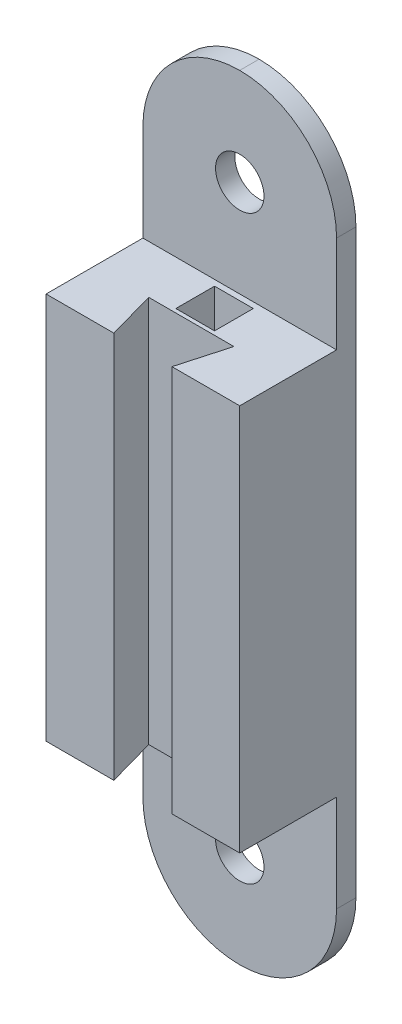
SolidWorks part; units mm, degrees
ref_plane "Front Plane" through (0, 0, 0) normal (0, 0, 1) x (1, 0, 0)
ref_plane "Top Plane" through (0, 0, 0) normal (0, 1, 0) x (1, 0, 0)
ref_plane "Right Plane" through (0, 0, 0) normal (1, 0, 0) x (0, 0, -1)
sketch "Sketch1" plane through (0, 0, 0) normal (0, 0, 1) x (1, 0, 0)
  line L0 (0, 0) -> (0, 25.4) construction
  line L1 (0, 25.4) -> (0, 50.8) construction
  line L2 (0, 0) -> (0, -25.4) construction
  line L3 (-12.7, 38.1) -> (12.7, 38.1)
  line L4 (-12.7, 63.5) -> (12.7, 63.5)
  line L5 (-12.7, 63.5) -> (-12.7, -38.1)
  line L6 (-12.7, -38.1) -> (12.7, -38.1)
  line L7 (12.7, 63.5) -> (12.7, -38.1)
  line L8 (-12.7, 63.5) -> (12.7, -38.1) construction
  line L9 (-12.7, -38.1) -> (12.7, 63.5) construction
  line L10 (-12.7, -12.7) -> (12.7, -12.7)
  circle A0 centre (0, -25.4) radius 3.175
  circle A3 centre (0, 50.8) radius 3.175
  point P9 (0, 12.7)
  point P15 (0, 38.1)
  point P18 (0, -12.7)
  dimension "D1" = 6.35
  dimension "D2" = 25.4
  dimension "D3" = 25.4
  dimension "D4" = 101.6
extrude "Boss-Extrude1" add sketch "Sketch1" along normal blind 2.54 contours L7 L4 L5 L3 A3 | L5 L10 L7 L3 | L10 L5 L6 L7 A0 region at (-12.3408, 50.8, 0) region at (0, 12.7, 0) region at (0, -13.0592, 0)
extrude "Boss-Extrude2" add sketch "Sketch1<3>" along normal blind 15.24 contours L5 L10 L7 L3 region at (0, 12.7, 0)
sketch "Sketch1<3>" plane through (0, 0, 0) normal (0, 0, 1) x (1, 0, 0) same geometry as "Sketch1"
sketch "Sketch3" plane through (0, 38.1, 0) normal (0, 1, 0) x (1, 0, 0)
  line L0 (-12.7, -15.24) -> (-3.81, -15.24)
  line L1 (-12.7, -15.24) -> (12.7, -15.24) construction
  line L2 (-3.81, -15.24) -> (-5.588, -8.89)
  line L3 (-5.588, -8.89) -> (5.588, -8.89)
  line L4 (5.588, -8.89) -> (3.81, -15.24)
  line L5 (3.81, -15.24) -> (12.7, -15.24)
  line L6 (-12.7, -15.24) -> (-12.7, -2.54)
  line L7 (-12.7, -2.54) -> (12.7, -2.54)
  line L8 (12.7, -2.54) -> (12.7, -15.24)
  line L9 (3.81, -15.24) -> (-3.81, -15.24)
  line M12 (-12.7, -15.24) -> (12.7, -15.24)
  dimension "D1" = 7.62
  dimension "D2" = 6.35
  dimension "D3" = 1.778
extrude "Cut-Extrude1" cut sketch "Sketch3" against normal through all contours L4 L3 L2 M12 region at (0, 38.1, 11.8648)
fillet "Fillet1" radius 12.7 4 edges at (12.7, -38.1, 1.27) (-12.7, -38.1, 1.27) (12.7, 63.5, 1.27) (-12.7, 63.5, 1.27)
sketch "Sketch4" plane through (0, 38.1, 0) normal (0, 1, 0) x (1, 0, 0)
  line L1 (-2.54, -3.302) -> (2.54, -3.302)
  line L2 (-2.54, -3.302) -> (-2.54, -8.382)
  line L3 (-2.54, -8.382) -> (2.54, -8.382)
  line L4 (2.54, -3.302) -> (2.54, -8.382)
  line L5 (-2.54, -3.302) -> (2.54, -8.382) construction
  line L6 (-2.54, -8.382) -> (2.54, -3.302) construction
  line L8 (-5.588, -8.89) -> (5.588, -8.89) construction
  point P0 (0, -5.842)
  point P5 (8.8486, -9.7151)
  point P6 (8.3612, -9.6963)
  point P7 (5.5116, -12.1522)
  point P8 (10.0109, -12.1522)
  point P9 (5.8678, -11.4773)
  point P10 (9.754, -11.8769)
  point P11 (7.7425, -9.2277)
  point P12 (4.7805, -11.2336)
  point P15 (7.8925, -8.9652)
  point P16 (11.118, -7.3247)
  point P17 (0, -5.8297)
  point P18 (0, 0)
  point P19 (7.9941, -9.0612)
  dimension "D1" = 5.08
  dimension "D2" = 5.08
  dimension "D3" = 0.508
extrude "Cut-Extrude2" cut sketch "Sketch4" against normal blind 20.32
